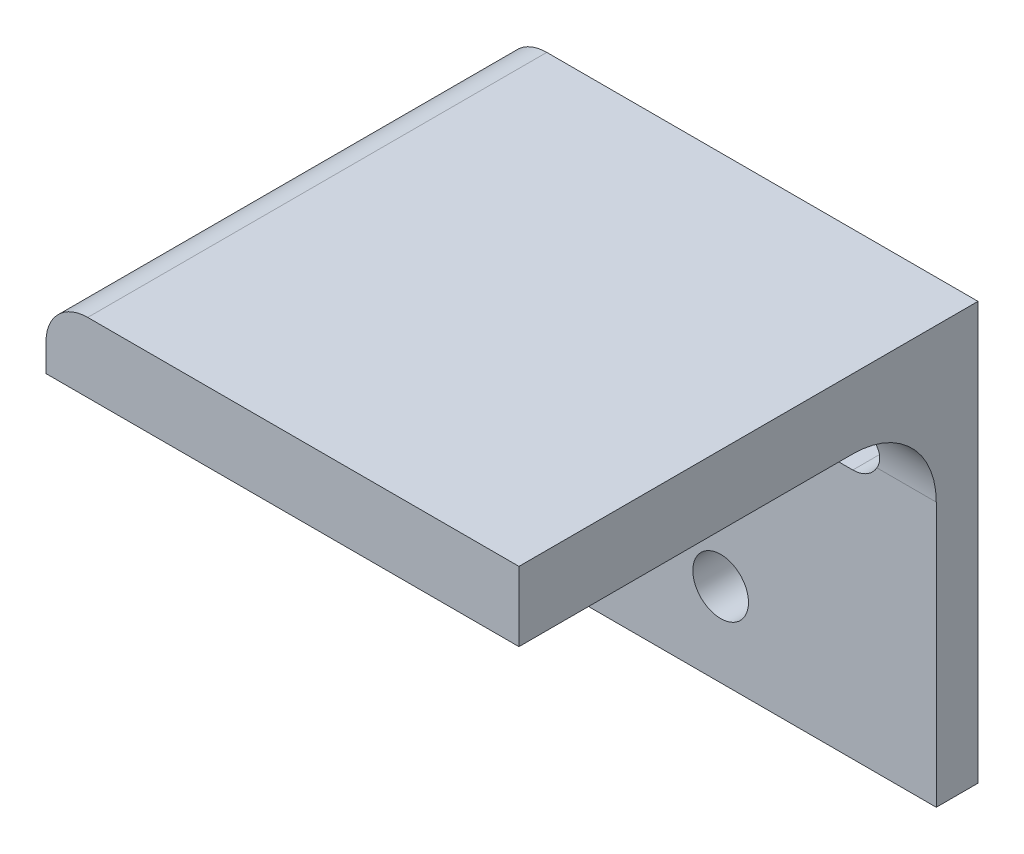
SolidWorks part; units mm, degrees
ref_plane "Plan de face" through (0, 0, 0) normal (0, 0, 1) x (1, 0, 0)
ref_plane "Plan de dessus" through (0, 0, 0) normal (0, 1, 0) x (1, 0, 0)
ref_plane "Plan de droite" through (0, 0, 0) normal (1, 0, 0) x (0, 0, -1)
sketch "Esquisse1" plane through (0, 0, 0) normal (0, 0, 1) x (1, 0, 0)
  line L0 (-5, 1.5) -> (23, 1.5)
  line L1 (-11, 7.5) -> (-11, 28.5)
  line L2 (23, 1.5) -> (23, 31.5)
  line L3 (-8, 31.5) -> (23, 31.5)
  line L11 (14, 23.5) -> (17, 23.5)
  line L13 (17, 19.5) -> (14, 19.5)
  circle A0 centre (-5, 7.5) radius 2
  circle A1 centre (7.5, 7.5) radius 2
  arc A2 (14, 23.5) -> (14, 19.5) centre (14, 21.5) ccw
  arc A3 (-5, 1.5) -> (-11, 7.5) centre (-5, 7.5) cw
  arc A4 (-11, 28.5) -> (-8, 31.5) centre (-8, 28.5) cw
  arc A7 (17, 19.5) -> (17, 23.5) centre (17, 21.5) ccw
  point P10 (-11, 1.5)
  point P13 (-11, 31.5)
  point P156 (0, 0)
  dimension "D2" = 3
  dimension "D7" = 6
  dimension "D12" = 4
  dimension "D10" = 6
  dimension "D11" = 3
  dimension "D3" = 6.5
  dimension "D4" = 14
  dimension "D5" = 12.5
  dimension "D6" = 6
  dimension "D8" = 30
  dimension "D9" = 6
extrude "Boss.-Extru.1" add sketch "Esquisse1" along normal blind 3
sketch "Esquisse2" plane through (0, 0, 3) normal (0, 0, 1) x (1, 0, 0)
  line L1 (-11, 28.5) -> (-11, 7.5) construction
  line L2 (23, 31.5) -> (-8, 31.5)
  line L3 (23, 31.5) -> (23, 26.5)
  line L4 (23, 26.5) -> (-11, 26.5)
  line L5 (-11, 28.5) -> (-11, 26.5)
  line L6 (23, 31.5) -> (-11, 26.5) construction
  line L7 (23, 26.5) -> (-11, 31.5) construction
  arc A0 (-8, 31.5) -> (-11, 28.5) centre (-8, 28.5) ccw
  point P16 (6, 29)
  dimension "D2" = 3
  dimension "D1" = 5
extrude "Boss.-Extru.2" add sketch "Esquisse2" along normal blind 30 contours L2 L5 L4 L3 region at (6.1877, 28.979, 3)
fillet "Congé1" radius 6 1 edges at (6, 26.5, 3)
